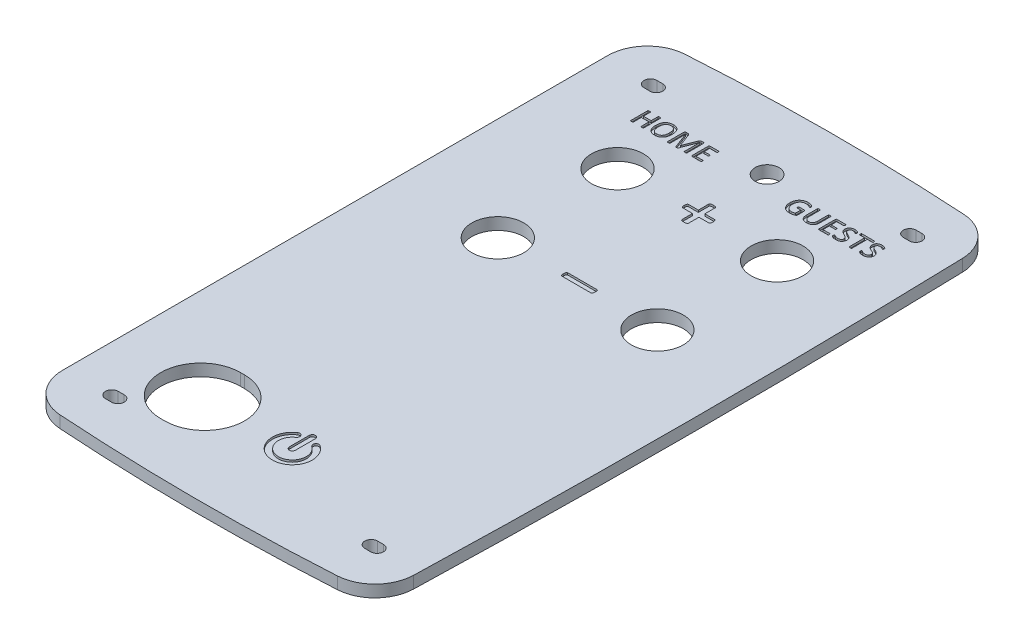
SolidWorks part; units mm, degrees
material "ABS"
ref_plane "Front Plane" through (0, 0, 0) normal (0, 0, 1) x (1, 0, 0)
ref_plane "Top Plane" through (0, 0, 0) normal (0, 1, 0) x (1, 0, 0)
ref_plane "Right Plane" through (0, 0, 0) normal (1, 0, 0) x (0, 0, -1)
sketch "Sketch1" plane through (0, 0, 0) normal (0, 1, 0) x (1, 0, 0)
  line L0 (0, 79.5) -> (0, 0) construction
  line L2 (-45.7963, 68.322) -> (-45.7963, -68.322)
  line L5 (0, 0) -> (0, -79.5) construction
  line L10 (-45.7963, 0) -> (0, 0) construction
  line L13 (43.7037, 0) -> (0, 0) construction
  arc A0 (42.7037, 68.809) -> (42.7037, -68.809) centre (-2324.1336, 0) cw
  arc A1 (-36.4595, 78.3) -> (33.3138, 78.5) centre (0, -470.3069) cw
  arc A2 (-36.4595, -78.3) -> (33.3138, -78.5) centre (0, 470.3069) ccw
  arc A3 (33.3138, 78.5) -> (42.7037, 68.809) centre (32.7079, 68.5184) cw
  arc A4 (42.7037, -68.809) -> (33.3138, -78.5) centre (32.7079, -68.5184) cw
  arc A5 (-36.4595, -78.3) -> (-45.7963, -68.322) centre (-35.7963, -68.322) cw
  arc A6 (-36.4595, 78.3) -> (-45.7963, 68.322) centre (-35.7963, 68.322) ccw
  dimension "D5" = 10
  dimension "D6" = 88.5
  dimension "D1" = 89.5
  dimension "D2" = 159
  dimension "D3" = 156.6
  dimension "D4" = 157
extrude "Boss-Extrude1" add sketch "Sketch1" along normal blind 3
extrude "Boss-Extrude2" add sketch "Sketch1<2>" against normal blind 17 separate body
sketch "Sketch1<2>" plane through (0, 0, 0) normal (0, 1, 0) x (1, 0, 0) same geometry as "Sketch1"
sketch "Sketch2" plane through (0, 3, 0) normal (0, 1, 0) x (1, 0, 0)
  line L0 (-33.5, 0) -> (0, 0) construction
  line L1 (-33.5, 67.5) -> (31.5, 67.5) construction
  line L2 (-33.5, 67.5) -> (-33.5, -67.5) construction
  line L3 (-33.5, -67.5) -> (31.5, -67.5) construction
  line L4 (31.5, 67.5) -> (31.5, -67.5) construction
  line L5 (0, 0) -> (31.5, 0) construction
  circle A0 centre (-33.5, 67.5) radius 1.6
  circle A1 centre (-33.5, -67.5) radius 1.6
  circle A2 centre (31.5, -67.5) radius 1.6
  circle A3 centre (31.5, 67.5) radius 1.6
  dimension "D1" = 3.2
  dimension "D2" = 135
  dimension "D3" = 65
  dimension "D4" = 31.5
extrude "Cut-Extrude1" cut sketch "Sketch2" against normal through all
sketch "Sketch3" plane through (0, 3, 0) normal (0, 1, 0) x (1, 0, 0)
  line L0 (20, 45) -> (20, 15) construction
  line L1 (-20, 45) -> (-20, 15) construction
  line L2 (20, 30) -> (-20, 30) construction
  line L3 (0, 30) -> (0, 0) construction
  line L4 (0, 0) -> (0, -56.5) construction
  line L5 (0, -56.5) -> (-22.5, -56.5) construction
  circle A0 centre (20, 45) radius 6.5
  circle A1 centre (-20, 45) radius 6.5
  circle A2 centre (20, 15) radius 6.5
  circle A3 centre (-20, 15) radius 6.5
  circle A4 centre (-22.5, -56.5) radius 10
  circle A5 centre (0, 62.5) radius 3
  dimension "D1" = 13
  dimension "D2" = 20
  dimension "D5" = 6
  dimension "D3" = 40
  dimension "D4" = 30
  dimension "D6" = 62.5
  dimension "D8" = 30
  dimension "D9" = 22.5
  dimension "D10" = 56.5
extrude "Cut-Extrude2" cut sketch "Sketch3" against normal through all
sketch "Sketch4" plane through (0, 3, 0) normal (0, 1, 0) x (1, 0, 0)
  line L0 (-23, -56.5) -> (-22, -56.5) construction
  line L1 (-23, -46.5) -> (-22, -46.5)
  line L2 (-23, -66.5) -> (-22, -66.5)
  line L3 (-22.5, -46.5) -> (-22.5, -56.5) construction
  line L4 (-22.5, -56.5) -> (-22.5, -66.5) construction
  line L5 (-34.25, -67.5) -> (-32.75, -67.5) construction
  line L8 (-34.25, -65.9) -> (-32.75, -65.9)
  line L9 (-34.25, -69.1) -> (-32.75, -69.1)
  line L10 (30.75, -67.5) -> (32.25, -67.5) construction
  line L11 (30.75, -65.9) -> (32.25, -65.9)
  line L12 (30.75, -69.1) -> (32.25, -69.1)
  line L13 (-33.5, -67.5) -> (31.5, -67.5) construction
  line L14 (-34.25, 67.5) -> (-32.75, 67.5) construction
  line L15 (-34.25, 69.1) -> (-32.75, 69.1)
  line L16 (-34.25, 65.9) -> (-32.75, 65.9)
  line L17 (30.75, 67.5) -> (32.25, 67.5) construction
  line L18 (30.75, 69.1) -> (32.25, 69.1)
  line L19 (30.75, 65.9) -> (32.25, 65.9)
  line L20 (-33.5, 67.5) -> (31.5, 67.5) construction
  arc A0 (-23, -46.5) -> (-23, -66.5) centre (-23, -56.5) ccw
  arc A1 (-22, -66.5) -> (-22, -46.5) centre (-22, -56.5) ccw
  circle A2 centre (-22.5, -56.5) radius 10 construction
  arc A6 (-34.25, -65.9) -> (-34.25, -69.1) centre (-34.25, -67.5) ccw
  arc A7 (-32.75, -69.1) -> (-32.75, -65.9) centre (-32.75, -67.5) ccw
  arc A8 (30.75, -65.9) -> (30.75, -69.1) centre (30.75, -67.5) ccw
  arc A9 (32.25, -69.1) -> (32.25, -65.9) centre (32.25, -67.5) ccw
  circle A11 centre (-33.5, -67.5) radius 1.6 construction
  arc A12 (-34.25, 69.1) -> (-34.25, 65.9) centre (-34.25, 67.5) ccw
  arc A13 (-32.75, 65.9) -> (-32.75, 69.1) centre (-32.75, 67.5) ccw
  arc A14 (30.75, 69.1) -> (30.75, 65.9) centre (30.75, 67.5) ccw
  arc A15 (32.25, 65.9) -> (32.25, 69.1) centre (32.25, 67.5) ccw
  point P2 (-22.5, -56.5)
  point P9 (-33.5, -67.5)
  point P21 (31.5, -67.5)
  point P28 (-33.5, 67.5)
  point P41 (31.5, 67.5)
  dimension "D1" = 1
  dimension "D2" = 1.5
extrude "Cut-Extrude3" cut sketch "Sketch4" against normal through all
sketch "Sketch6" plane through (0, 3, 0) normal (0, 1, 0) x (1, 0, 0)
  line L0 (-40, 57) -> (0, 57) construction
  line L1 (0, 57) -> (0, 41) construction
  line L2 (0, 57) -> (40, 57) construction
  line L3 (-20, 45) -> (-20, 57) construction
  line L4 (-10, 41) -> (10, 41) construction
  line L5 (-10, 17.5) -> (10, 17.5) construction
  line L6 (0, 41) -> (0, 17.5) construction
  line L7 (0, 17.5) -> (0, 0) construction
  line L8 (-10, 41) -> (-10, 49) construction
  line L9 (-10, 49) -> (10, 49) construction
  line L10 (10, 49) -> (10, 41) construction
  line L11 (-20, 45) -> (-10, 45) construction
  line L12 (-10, 17.5) -> (-10, 25.5) construction
  line L13 (-10, 25.5) -> (10, 25.5) construction
  line L14 (10, 25.5) -> (10, 17.5) construction
  line L15 (0, -56.5) -> (-22.5, -56.5) construction
  line L16 (-23, -56.5) -> (-22, -56.5) construction
  line L17 (0, -51.5) -> (0, -56.5) construction
  line L18 (0.75, -51.5) -> (0.75, -56.5)
  line L19 (-0.75, -51.5) -> (-0.75, -56.5)
  line L20 (-2.4109, -53) -> (2.4109, -53) construction
  arc A0 (-2.8364, -52.3824) -> (2.8364, -52.3824) centre (0, -56.5) ccw
  arc A1 (-1.9855, -53.6176) -> (1.9855, -53.6176) centre (0, -56.5) ccw
  arc A2 (0.75, -51.5) -> (-0.75, -51.5) centre (0, -51.5) ccw
  arc A3 (-2.8364, -52.3824) -> (-1.9855, -53.6176) centre (-2.4109, -53) cw
  arc A4 (1.9855, -53.6176) -> (2.8364, -52.3824) centre (2.4109, -53) cw
  arc A5 (-0.75, -56.5) -> (0.75, -56.5) centre (0, -56.5) ccw
  text T0 "HOME" font "Calibri" height 4.5
  text T1 "GUESTS" font "Calibri" height 4.5
  text T2 "+" font "Calibri" height 10
  text T3 "_" font "Calibri" height 10
  point P22 (0, -54)
  dimension "D6" = 10
  dimension "D7" = 1.5
  dimension "D1" = 57
  dimension "D2" = 8
  dimension "D3" = 20
  dimension "D4" = 17.5
  dimension "D8" = 3.5
  dimension "D9" = 5
extrude "Cut-Extrude4" cut sketch "Sketch6" against normal blind 0.5
sketch "Sketch7" plane through (0, 0, 0) normal (0, -1, 0) x (1, 0, 0)
  line L1 (47.0159, 90.2111) -> (-54.2671, 90.2111)
  line L2 (47.0159, 90.2111) -> (47.0159, -88.4496)
  line L3 (47.0159, -88.4496) -> (-54.2671, -88.4496)
  line L4 (-54.2671, 90.2111) -> (-54.2671, -88.4496)
extrude "Cut-Extrude5" cut sketch "Sketch7" along normal blind 20
ref_plane "Plane1" through (-34.25, 0, 0) normal (1, 0, 0) x (0, 0, -1)
ref_plane "Plane2" through (32.25, 0, 0) normal (1, 0, 0) x (0, 0, -1)
ref_plane "Plane3" through (-1, 0, 0) normal (1, 0, 0) x (0, 0, -1)
